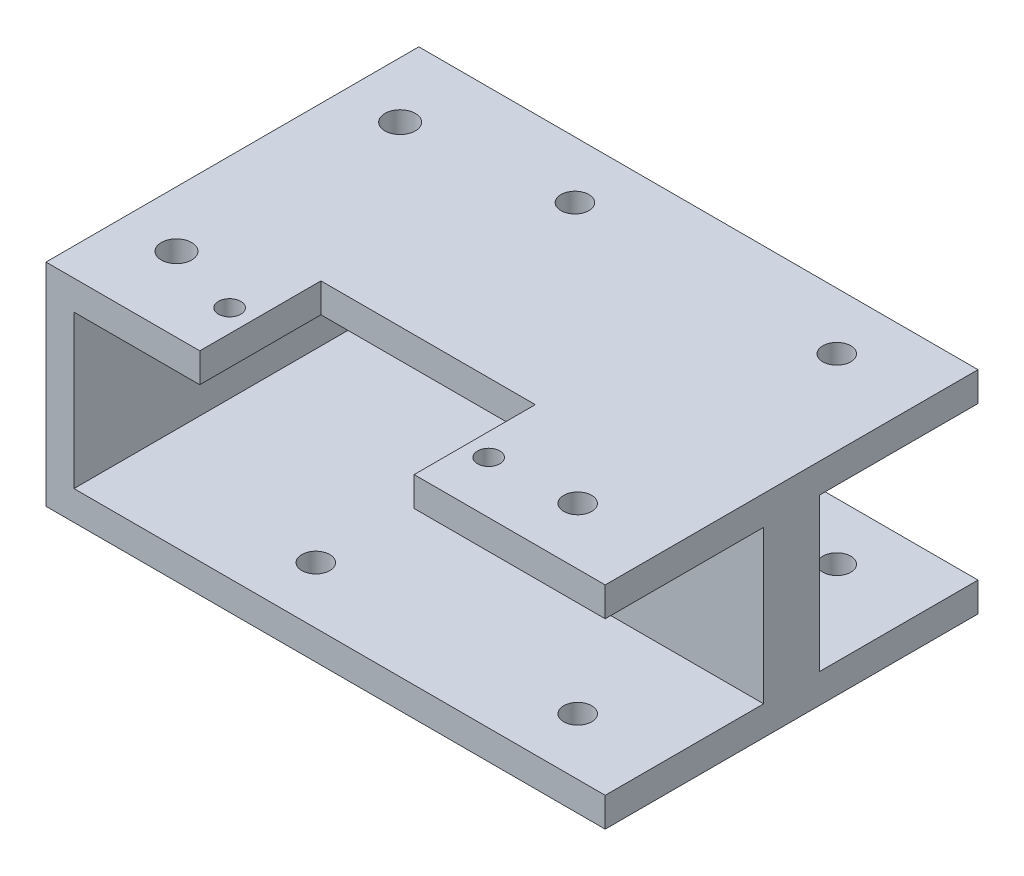
SolidWorks part; units mm, degrees
note: The reader was unsure of these and kept them because the rebuilt part matched: shared geometry of "Sketch1<2>".
ref_plane "Front Plane" through (0, 0, 0) normal (0, 0, 1) x (1, 0, 0)
ref_plane "Top Plane" through (0, 0, 0) normal (0, 1, 0) x (1, 0, 0)
ref_plane "Right Plane" through (0, 0, 0) normal (1, 0, 0) x (0, 0, -1)
sketch "Sketch1" plane through (0, 0, 0) normal (0, 1, 0) x (1, 0, 0)
  line L1 (0, 20) -> (60, 20)
  line L2 (0, 20) -> (0, -20)
  line L3 (0, -20) -> (60, -20)
  line L4 (60, 20) -> (60, -20)
  point P4 (0, 0)
  dimension "D1" = 60
  dimension "D2" = 40
extrude "Boss-Extrude1" add sketch "Sketch1" against normal blind 3.15
extrude "Boss-Extrude2" add sketch "Sketch1<2>" along normal blind 3.15 from offset 16.4 separate body
sketch "Sketch1<2>" plane through (0, 0, 0) normal (0, 1, 0) x (1, 0, 0) same geometry as "Sketch1"
sketch "Sketch2" plane through (0, 0, 0) normal (0, 1, 0) x (1, 0, 0)
  line L0 (0, -20) -> (60, -20) construction
  line L1 (0, 20) -> (3, 20)
  line L2 (0, 20) -> (0, -20)
  line L3 (0, -20) -> (3, -20)
  line L4 (3, 20) -> (3, -20)
  line L5 (60, -20) -> (60, 20) construction
  line L6 (60, 3) -> (40, 3)
  line L7 (60, 3) -> (60, -3)
  line L8 (60, -3) -> (40, -3)
  line L9 (40, 3) -> (40, -3)
  point P14 (60, 0)
  dimension "D2" = 6
  dimension "D3" = 20
extrude "Boss-Extrude3" add sketch "Sketch2" along normal up to surface (16.4 mm away) up to face at (30, 16.4, 0)
sketch "Sketch3" plane through (0, 0, 0) normal (-1, 0, 0) x (0, 0, 1)
  line L0 (-20, 19.55) -> (20, 19.55) construction
  line L1 (-3, 19.55) -> (3, 19.55)
  line L2 (-3, 19.55) -> (-3, -3.15)
  line L3 (-3, -3.15) -> (3, -3.15)
  line L4 (3, 19.55) -> (3, -3.15)
  line L5 (-20, -3.15) -> (20, -3.15) construction
  point P8 (0, 19.55)
  dimension "D3" = 6
extrude "Boss-Extrude4" [suppressed] add sketch "Sketch3" along normal blind 40
hole_wizard "M2 Clearance Hole1" positions "Sketch7" profile "Sketch9" hole size "M2" standard "ANSI Metric"
sketch "Sketch7" plane through (0, 19.55, 0) normal (0, 1, 0) x (1, 0, 0)
  line L1 (0, -20) -> (60, -20) construction
  line L2 (60, -20) -> (60, 20) construction
  point P0 (14.1, -14.4)
  point P2 (41.9, -14.4)
  point P5 (14.1, -14.4)
  point P7 (41.9, -14.4)
  dimension "D1" = 27.8
  dimension "D3" = 5.6
  dimension "D2" = 18.1
sketch "Sketch9" plane through (14.1, 19.55, 14.4) normal (1, 0, 0) x (0, 0, 1)
  line L0 (0, 0) -> (0, 5.721)
  line L1 (0, 5.721) -> (1.2, 5)
  line L2 (1.2, 5) -> (1.2, 0)
  line L5 (1.2, 0) -> (0, 0)
  line L10 (0, 5.721) -> (-1.2, 5) construction
  line L11 (0, -6.35) -> (0, 107.95) construction
  dimension "Hole Dia." = 2.4
  dimension "Hole Depth" = 5
  dimension "Drill Angle" = 118
hole_wizard "Ø3.0mm Dowel Hole1" positions "Sketch10" profile "Sketch11" hole size "Ø3.0" standard "ANSI Metric" end condition through all
sketch "Sketch10" plane through (0, 19.55, 0) normal (0, 1, 0) x (1, 0, 0)
  line L0 (0, -20) -> (60, -20) construction
  line L1 (60, -20) -> (60, 20) construction
  point P0 (50.95, -13.9)
  point P7 (22.85, 13.9)
  point P13 (50.95, 13.9)
  point P14 (22.85, -13.9)
  dimension "D1" = 6.1
  dimension "D2" = 9.05
  dimension "D4" = 37.15
  dimension "D3" = 27.8
sketch "Sketch11" plane through (50.95, 19.55, 13.9) normal (1, 0, 0) x (0, 0, 1)
  line L0 (0, 0) -> (0, 22.7)
  line L1 (0, 22.7) -> (1.5, 22.7)
  line L2 (1.5, 22.7) -> (1.5, 0)
  line L5 (1.5, 0) -> (0, 0)
  line L11 (0, -6.35) -> (0, 107.95) construction
  dimension "Thru Hole Dia." = 3
  dimension "Thru Hole Depth" = 22.7
sketch "Sketch5" plane through (0, 19.55, 0) normal (0, 1, 0) x (1, 0, 0)
  line L0 (0, -20) -> (60, -20) construction
  line L1 (16.5, -20) -> (39.5, -20)
  line L2 (16.5, -20) -> (16.5, -7)
  line L3 (16.5, -7) -> (39.5, -7)
  line L4 (39.5, -20) -> (39.5, -7)
  circle A0 centre (41.9, -14.4) radius 1.2 construction
  point P6 (28, -7)
  dimension "D1" = 23
  dimension "D2" = 13.9
  dimension "D3" = 13
extrude "Cut-Extrude1" cut sketch "Sketch5" against normal blind 7
fillet "Fillet1" [suppressed] radius 1
hole_wizard "#4 Clearance Hole1" [suppressed] positions "Sketch14" profile "Sketch15" hole size "#4" standard "ANSI Inch"
sketch "Sketch14" [suppressed] plane through (0, 0, 3) normal (0, 0, 1) x (1, 0, 0)
  line L0 (-40, -2.15) -> (-40, 18.55) construction
  point P0 (-35, 8.2)
  point P2 (-8.82, 8.2)
  point P7 (-40, 8.2)
  dimension "D1" = 26.18
  dimension "D2" = 5
sketch "Sketch15" plane through (-35, 8.2, 3) normal (1, 0, 0) x (0, -1, 0)
  line L0 (0, 0) -> (0, 23)
  line L1 (0, 23) -> (1.6319, 23)
  line L2 (1.6319, 23) -> (1.6319, 0)
  line L5 (1.6319, 0) -> (0, 0)
  line L11 (0, -6.35) -> (0, 107.95) construction
  dimension "Thru Hole Dia." = 3.2639
  dimension "Thru Hole Depth" = 23
hole_wizard "#2 Clearance Hole1" [suppressed] positions "Sketch16" profile "Sketch17" hole size "#2" standard "ANSI Inch"
sketch "Sketch16" [suppressed] plane through (0, 0, 3) normal (0, 0, 1) x (1, 0, 0)
  line L0 (-40, -2.15) -> (-40, 18.55) construction
  circle A0 centre (-35, 8.2) radius 1.632 construction
  point P0 (-21.91, 8.2)
  point P8 (-40, 8.2)
  dimension "D1" = 13.09
sketch "Sketch17" plane through (-21.91, 8.2, 3) normal (1, 0, 0) x (0, -1, 0)
  line L0 (0, 0) -> (0, 23)
  line L1 (0, 23) -> (1.2192, 23)
  line L2 (1.2192, 23) -> (1.2192, 0)
  line L5 (1.2192, 0) -> (0, 0)
  line L11 (0, -6.35) -> (0, 107.95) construction
  dimension "Thru Hole Dia." = 2.4384
  dimension "Thru Hole Depth" = 23
hole_wizard "#4 Clearance Hole2" positions "Sketch18" profile "Sketch19" hole size "#4" standard "ANSI Inch"
sketch "Sketch18" plane through (0, 19.55, 0) normal (0, 1, 0) x (1, 0, 0)
  point P0 (6, 12)
  point P2 (6, -12)
  point P6 (0, 0)
  dimension "D1" = 12
  dimension "D2" = 12
  dimension "D3" = 6
sketch "Sketch19" plane through (6, 19.55, -12) normal (1, 0, 0) x (0, 0, 1)
  line L0 (0, 0) -> (0, 10.9806)
  line L1 (0, 10.9806) -> (1.6319, 10)
  line L2 (1.6319, 10) -> (1.6319, 0)
  line L5 (1.6319, 0) -> (0, 0)
  line L10 (0, 10.9806) -> (-1.632, 10) construction
  line L11 (0, -6.35) -> (0, 107.95) construction
  dimension "Hole Dia." = 3.2639
  dimension "Hole Depth" = 10
  dimension "Drill Angle" = 118
equation "\"D2@Sketch7\"=9.05*2"
equation "\"D1@Sketch10\"=(40-\"D3@Sketch10\")/2"
equation "\"D3@Sketch7\"=5.6"
equation "\"D2@Sketch18\"=\"D1@Sketch18\""
